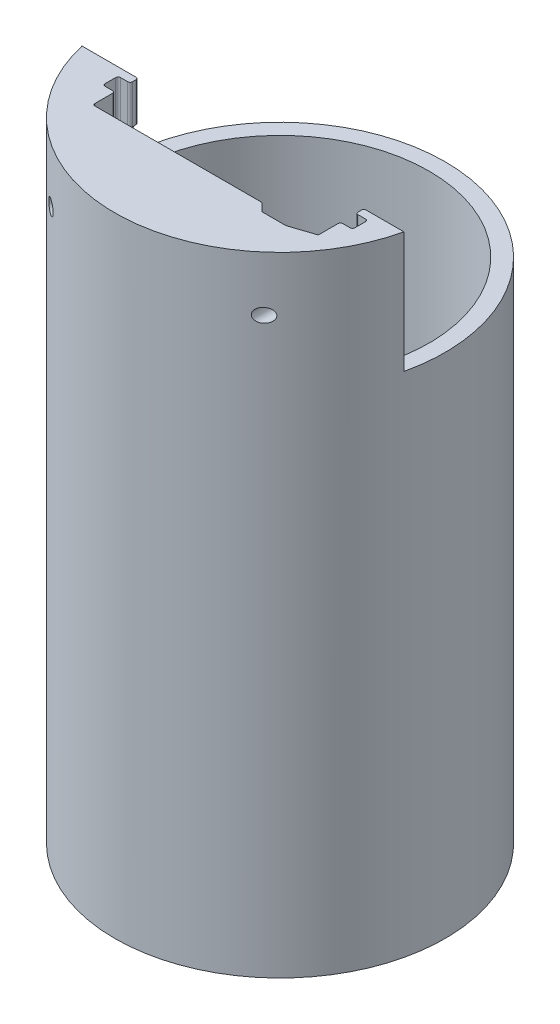
SolidWorks part; units mm, degrees
ref_plane "Front Plane" through (0, 0, 0) normal (0, 0, 1) x (1, 0, 0)
ref_plane "Top Plane" through (0, 0, 0) normal (0, 1, 0) x (1, 0, 0)
ref_plane "Right Plane" through (0, 0, 0) normal (1, 0, 0) x (0, 0, -1)
sketch "Sketch1" plane through (0, 0, 0) normal (0, 1, 0) x (1, 0, 0)
  circle A0 centre (0, 0) radius 20.5
  circle A1 centre (0, 0) radius 7.5
  dimension "D1" = 41
  dimension "D2" = 15
extrude "Boss-Extrude1" add sketch "Sketch1" along normal blind 3
sketch "Sketch3" plane through (0, 0, 0) normal (0, -1, 0) x (1, 0, 0)
  line L0 (0, 0) -> (0, 14.35) construction
  circle A0 centre (0, 14.35) radius 1.4
  dimension "D2" = 2.8
  dimension "D1" = 14.35
extrude "Cut-Extrude1" cut sketch "Sketch3" against normal blind 5
chamfer "Chamfer6" distance 0.3 angle 45 1 edges at (0, 0, 12.95)
pattern_circular "CirPattern2" count 4 over 360 about axis through (0, 0, 0) along (0, 1, 0) of "Chamfer6", "Cut-Extrude1"
sketch "Sketch4" plane through (0, 3, 0) normal (0, 1, 0) x (1, 0, 0)
  line L0 (0, 0) -> (0, -2) construction
  line L1 (-13, -7.5) -> (-14.5, -7.5) construction
  line L6 (-14.5, -5.6) -> (16.5, -5.6)
  line L7 (-14.5, -5.6) -> (-14.5, -7.5)
  line L8 (-14.5, -7.5) -> (16.5, -7.5)
  line L9 (16.5, -5.6) -> (16.5, -7.5)
  line L10 (-13, -7.5) -> (15, -7.5)
  line L11 (-13, -7.5) -> (-13, -10.25)
  line L12 (-13, -10.25) -> (15, -10.25)
  line L13 (15, -7.5) -> (15, -10.25)
  line L14 (15, -7.5) -> (16.5, -7.5) construction
  line L15 (15, -10.25) -> (12, -11.25)
  line L16 (15, -10.25) -> (9, -10.25)
  line L17 (15, -10.25) -> (15, -11.25)
  line L18 (15, -11.25) -> (9, -11.25)
  line L19 (9, -10.25) -> (9, -11.25)
  line L20 (16.5, -4.6) -> (15, -4.6)
  line L21 (-14.5, -5.6) -> (-13, -5.6)
  line L22 (-14.5, -5.6) -> (-14.5, -4.6)
  line L23 (-14.5, -4.6) -> (-13, -4.6)
  line L24 (-13, -5.6) -> (-13, -4.6)
  line L25 (15, -5.6) -> (15, -4.6)
  line L26 (16.5, -5.6) -> (15, -5.6)
  line L27 (16.5, -5.6) -> (16.5, -4.6)
  line L28 (-14.5, -4.6) -> (-17.919, -4.6)
  line L29 (16.5, -4.6) -> (17.919, -4.6)
  line L30 (1, 0) -> (1, -5.6) construction
  line L31 (0, 0) -> (1, 0) construction
  circle A0 centre (0, 0) radius 20.5
  circle A2 centre (0, 0) radius 20.5 construction
  circle A3 centre (0, 0) radius 18.5
  circle M10 centre (0, -14.35) radius 1.4
  circle M11 centre (0, 0) radius 20.5
  dimension "D8" = 2
  dimension "D2" = 31
  dimension "D3" = 1.9
  dimension "D4" = 1.5
  dimension "D5" = 2.75
  dimension "D6" = 6
  dimension "D7" = 1
  dimension "D9" = 1
  dimension "D10" = 1.5
  dimension "D11" = 5.6
  dimension "D12" = 1
  dimension "D13" = 2
extrude "Boss-Extrude2" add sketch "Sketch4" along normal blind 60 contours L6 L24 L23 L22 | L6 L27 L20 L25 | L18 A3 L17 L15 | L17 A3 L29 L27 L9 L8 L13 | L28 A3 L18 L19 L12 L11 L8 L7 L22 M10 | A3 L17 L18 M11 | M10 | A3 L18 L17 region at (-13.75, 3, 5.1) region at (-1.8436, 3, 13.103) region at (15.75, 3, 5.1) region at (16.5688, 3, 5.1) region at (14.896, 3, 11.1101) region at (13.9591, 3, 10.9078) region at (-19.9202, 3, 0) region at (0, 3, 14.35)
sketch "Sketch6" plane through (0, 63, 0) normal (0, 1, 0) x (1, 0, 0)
  line L0 (-17.919, -4.6) -> (-14.5, -4.6)
  line L1 (-14.5, -5.6) -> (16.5, -5.6)
  line L2 (-14.5, -5.6) -> (-14.5, -7.5)
  line L3 (-14.5, -7.5) -> (16.5, -7.5)
  line L4 (16.5, -5.6) -> (16.5, -7.5)
  line L5 (-13, -7.5) -> (15, -7.5)
  line L6 (-13, -7.5) -> (-13, -10.25)
  line L7 (-13, -10.25) -> (15, -10.25)
  line L8 (15, -7.5) -> (15, -10.25)
  line L9 (-14.5, -4.6) -> (-13, -4.6)
  line L10 (-14.5, -4.6) -> (-14.5, -5.6)
  line L11 (-14.5, -5.6) -> (-13, -5.6)
  line L12 (-13, -4.6) -> (-13, -5.6)
  line L13 (15, -4.6) -> (16.5, -4.6)
  line L14 (15, -4.6) -> (15, -5.6)
  line L15 (15, -5.6) -> (16.5, -5.6)
  line L16 (16.5, -4.6) -> (16.5, -5.6)
  line L17 (16.5, -4.6) -> (17.919, -4.6)
  line L18 (12, -11.25) -> (15, -10.25)
  line L19 (9, -10.25) -> (15, -10.25)
  line L20 (9, -10.25) -> (9, -11.25)
  line L21 (9, -11.25) -> (15, -11.25)
  line L22 (15, -10.25) -> (15, -11.25)
  line L23 (-19.9772, -4.6) -> (-17.919, -4.6)
  line L24 (17.919, -4.6) -> (19.9772, -4.6)
  circle A0 centre (0, 0) radius 18.5
  circle A1 centre (0, 0) radius 18.5 construction
  circle A2 centre (0, 0) radius 20.5
  circle A3 centre (0, 0) radius 20.5 construction
  line M12 (17.919, -4.6) -> (15, -4.6)
  line M13 (15, -4.6) -> (15, -5.6)
  line M14 (15, -5.6) -> (16.5, -5.6)
  line M15 (16.5, -5.6) -> (16.5, -7.5)
  line M16 (16.5, -7.5) -> (15, -7.5)
  line M17 (15, -7.5) -> (15, -10.25)
  line M20 (12, -11.25) -> (9, -11.25)
  line M21 (9, -11.25) -> (9, -10.25)
  line M22 (9, -10.25) -> (-13, -10.25)
  line M23 (-13, -10.25) -> (-13, -7.5)
  line M24 (-13, -7.5) -> (-14.5, -7.5)
  line M25 (-14.5, -7.5) -> (-14.5, -5.6)
  line M26 (-14.5, -5.6) -> (-13, -5.6)
  line M27 (-13, -5.6) -> (-13, -4.6)
  line M28 (-13, -4.6) -> (-17.919, -4.6)
  circle M29 centre (0, 0) radius 20.5
  line M50 (15, -10.25) -> (12, -11.25)
extrude "Boss-Extrude4" add sketch "Sketch6" along normal blind 15 contours L10 M28 M26 M27 | L16 M12 M13 M14 | A0 L21 L10 M28 M20 M21 M22 M23 M24 M25 | A0 L21 L22 | L22 A0 L16 M12 M15 M16 M17 | A0 L22 L21 L23 L24 M29 | L21 A0 L22 M50 region at (-3.783, 63, 18.5482) region at (-1.7839, 63, 13.1434) region at (-13.75, 63, 5.1) region at (14.896, 63, 11.1101) region at (13.9591, 63, 10.9078) region at (16.6892, 63, 7.8218) region at (15.75, 63, 5.1)
fillet "Fillet1" radius 0.3 11 edges at (15, 40.5, 4.6) (15, 40.5, 5.6) (16.5, 40.5, 5.6) (16.5, 40.5, 7.5) (15, 40.5, 7.5) (-13, 40.5, 10.25) (-13, 40.5, 7.5) (-14.5, 40.5, 7.5) (-14.5, 40.5, 5.6) (-13, 40.5, 5.6) (-13, 40.5, 4.6)
sketch "Sketch7" plane through (0, 0, 4.6) normal (0, 0, -1) x (-1, 0, 0)
  line L0 (11.45, 3) -> (11.45, 71.2) construction
  line L1 (13, 78) -> (14.5, 78) construction
  line L2 (13, 78) -> (13, 3) construction
  line L3 (13, 3) -> (14.5, 3) construction
  line L4 (14.5, 78) -> (14.5, 3) construction
  line L5 (14.5, 3) -> (13, 3) construction
  circle A0 centre (11.45, 71.2) radius 2.5
  point P6 (0, 0)
  point P11 (0, 0)
  point P12 (0, 0)
  point P16 (0, 0)
  dimension "D2" = 5
  dimension "D1" = 68.2
  dimension "D3" = 3.05
extrude "Cut-Extrude2" cut sketch "Sketch7" against normal offset from surface (1.5 mm away) 0.5 up to face at (-13.75, 40.5, 5.6) offset beyond the face yes
sketch "Sketch8" plane through (0, 0, 7.5) normal (0, 0, -1) x (-1, 0, 0)
  line L0 (-1, 3) -> (-1, 91.8738) construction
  circle A0 centre (11.45, 71.2) radius 0.85
  point P5 (0, 0)
  point P7 (0, 0)
  dimension "D1" = 1.7
extrude "Cut-Extrude3" cut sketch "Sketch8" against normal through all
ref_plane "Plane1" through (1, 0, 0) normal (1, 0, 0) x (0, 0, -1)
chamfer "Chamfer2" distance 0.2 angle 45 1 edges at (-12.3, 71.2, 10.25)
mirror "Mirror3" about plane through (1, 0, 0) normal (1, 0, 0) of "Cut-Extrude3", "Cut-Extrude2"
chamfer "Chamfer4" distance 1 angle 45 1 edges at (9, 40.5, 10.25)
fillet "Chamfer5" radius 0.2 1 edges at (14.3, 71.2, 10.4833)
sketch "Sketch9" plane through (0, 3, 0) normal (0, -1, 0) x (1, 0, 0)
  circle A1 centre (0, 14.35) radius 1.4
  circle A2 centre (0, 14.35) radius 1.4 construction
extrude "Cut-Extrude4" cut sketch "Sketch9" against normal blind 5
equation "\"0.2mmmm\"=1"
